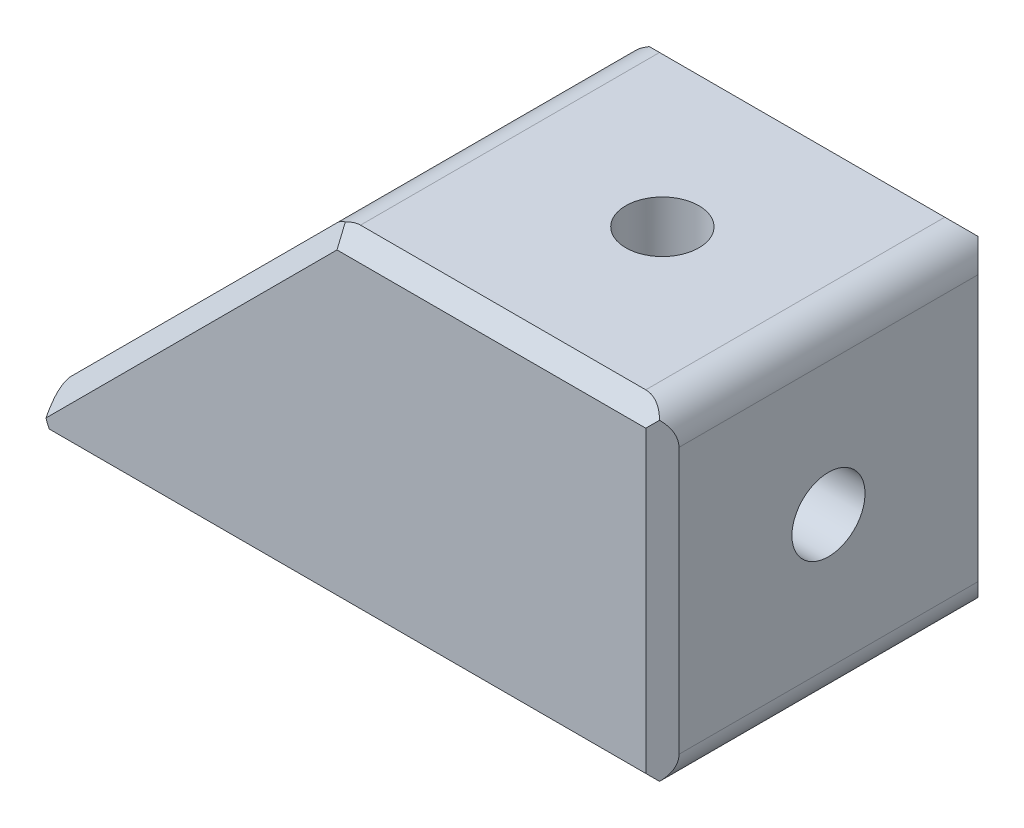
SolidWorks part; units mm, degrees
material "PETG"
ref_plane "Płaszczyzna przednia" through (0, 0, 0) normal (0, 0, 1) x (1, 0, 0)
ref_plane "Płaszczyzna górna" through (0, 0, 0) normal (0, 1, 0) x (1, 0, 0)
ref_plane "Płaszczyzna prawa" through (0, 0, 0) normal (1, 0, 0) x (0, 0, -1)
sketch "Sketch1" plane through (0, 0, 0) normal (0, 0, 1) x (1, 0, 0)
  line L1 (0, 0) -> (40, 0)
  line L2 (0, 0) -> (0, 20)
  line L3 (0, 20) -> (40, 20)
  line L4 (40, 0) -> (40, 20)
  dimension "D1" = 20
  dimension "D2" = 40
extrude "Boss-Extrude1" add sketch "Sketch1" along normal blind 20
hole_wizard "Ø4.4 (4.4) Diameter Hole1" positions "Sketch2" profile "Sketch3" hole size "Ø4.4" standard "DIN" end condition through all
sketch "Sketch2" plane through (0, 0, 0) normal (-1, 0, 0) x (0, 0, 1)
  line L1 (0, 0) -> (10, 10) construction
  line L2 (10, 10) -> (20, 20) construction
  point P0 (10, 10)
sketch "Sketch3" plane through (0, 10, 10) normal (0, 1, 0) x (0, 0, 1)
  line L0 (0, 0) -> (0, 40)
  line L1 (0, 40) -> (2.2, 40)
  line L2 (2.2, 40) -> (2.2, 0)
  line L5 (2.2, 0) -> (0, 0)
  line L11 (0, -6.35) -> (0, 107.95) construction
  dimension "Thru Hole Dia." = 4.4
  dimension "Thru Hole Depth" = 40
hole_wizard "Ø4.4 (4.4) Diameter Hole2" positions "Sketch4" profile "Sketch5" hole size "Ø4.4" standard "DIN" end condition through all
sketch "Sketch4" plane through (0, 0, 0) normal (0, -1, 0) x (-1, 0, 0)
  line L3 (-40, -20) -> (-40, 0) construction
  point P0 (-30, -10)
  dimension "D1" = 10
sketch "Sketch5" plane through (30, 0, 10) normal (1, 0, 0) x (0, 0, -1)
  line L0 (0, 0) -> (0, 20)
  line L1 (0, 20) -> (2.2, 20)
  line L2 (2.2, 20) -> (2.2, 0)
  line L5 (2.2, 0) -> (0, 0)
  line L11 (0, -6.35) -> (0, 107.95) construction
  dimension "Thru Hole Dia." = 4.4
  dimension "Thru Hole Depth" = 20
hole_wizard "Ø4.4 (4.4) Diameter Hole3" positions "Sketch7" profile "Sketch8" hole size "Ø4.4" standard "DIN" end condition through all
sketch "Sketch7" plane through (0, 0, 0) normal (0, -1, 0) x (-1, 0, 0)
  line L0 (-10, -20) -> (-10, -10) construction
  line L1 (0, -20) -> (-40, -20) construction
  line L2 (-10, -10) -> (-10, 0) construction
  line L3 (0, 0) -> (-40, 0) construction
  line L5 (-40, -20) -> (-40, 0) construction
  point P0 (-10, -10)
  dimension "D1" = 30
sketch "Sketch8" plane through (10, 0, 10) normal (1, 0, 0) x (0, 0, -1)
  line L0 (0, 0) -> (0, 20)
  line L1 (0, 20) -> (2.2, 20)
  line L2 (2.2, 20) -> (2.2, 0)
  line L5 (2.2, 0) -> (0, 0)
  line L11 (0, -6.35) -> (0, 107.95) construction
  dimension "Thru Hole Dia." = 4.4
  dimension "Thru Hole Depth" = 20
sketch "Sketch6" plane through (0, 0, 0) normal (0, 0, -1) x (-1, 0, 0)
  line L0 (-20, 20) -> (-20, 12.5) construction
  line L1 (-40, 20) -> (0, 20) construction
  line L2 (0, 10) -> (-7.5, 10) construction
  line L3 (0, 20) -> (0, 0) construction
  line L4 (-6.9562, 12.4) -> (-6.9562, 10) construction
  line L9 (0, 7.6) -> (-7.5, 7.6) construction
  line L10 (0, 7.6) -> (0, 12.4) construction
  line L11 (0, 12.4) -> (-7.5, 12.4) construction
  line L12 (-7.5, 7.6) -> (-7.5, 12.4) construction
  line L13 (-6.9562, 10) -> (-6.9562, 7.6) construction
  line L14 (0, 0) -> (-40, 20) construction
  line L15 (0, 20) -> (-40, 0) construction
  line L16 (-7.6, 20) -> (-17.6, 12.5) construction
  line L17 (-7.6, 20) -> (-12.4, 20) construction
  line L18 (-12.4, 20) -> (-22.4, 12.5) construction
  line L19 (-17.6, 12.5) -> (-22.4, 12.5) construction
  line L20 (-40, 20) -> (0, 0)
  line L21 (0, 0) -> (-40, 0)
  line L22 (-40, 0) -> (-40, 20)
  point P27 (-20, 12.5)
  dimension "D2" = 7.5
  dimension "D3" = 4.8
extrude "Cut-Extrude1" [suppressed] cut sketch "Sketch6" against normal through all
sketch "Sketch9" plane through (0, 0, 0) normal (0, 0, -1) x (-1, 0, 0)
  line L0 (0, 0) -> (-20, 20)
  line L1 (-40, 20) -> (0, 20) construction
  line L2 (-20, 20) -> (0, 20)
  line L3 (0, 20) -> (0, 0)
  dimension "D1" = 20
extrude "Cut-Extrude2" cut sketch "Sketch9" against normal through all
fillet "Fillet1" [suppressed] radius 1.5
chamfer "Chamfer2" [suppressed] distance 1 angle 45
chamfer "Chamfer3" distance 1 angle 45 8 edges at (20, 0, 0) (40, 10, 0) (30, 20, 0) (10, 10, 0) (20, 0, 20) (40, 10, 20) (30, 20, 20) (10, 10, 20)
fillet "Fillet2" radius 2 4 edges at (0, 0, 10) (20, 20, 10) (40, 20, 10) (40, 0, 10)
